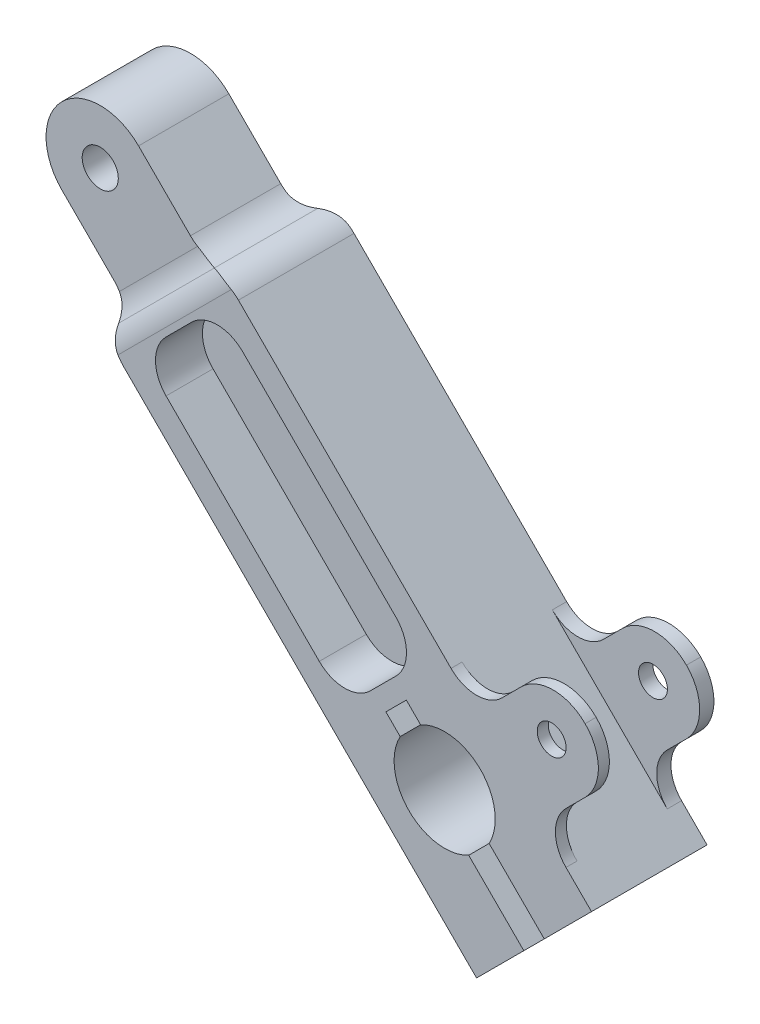
SolidWorks part; units mm, degrees
ref_plane "Front Plane" through (0, 0, 0) normal (0, 0, 1) x (1, 0, 0)
ref_plane "Top Plane" through (0, 0, 0) normal (0, 1, 0) x (1, 0, 0)
ref_plane "Right Plane" through (0, 0, 0) normal (1, 0, 0) x (0, 0, -1)
sketch "Sketch2" plane through (0, 0, 0) normal (0, 0, 1) x (1, 0, 0)
  line L0 (0, 0) -> (-234.0257, 0) construction
  line L1 (0, 0) -> (132.15, 132.15) construction
  line L2 (0, 0) -> (130.2279, -130.2279) construction
  line L3 (-10.6066, -10.6066) -> (10.6066, 10.6066) construction
  line L4 (-10.6066, -10.6066) -> (21.2132, -42.4264) construction
  line L5 (21.2132, -42.4264) -> (42.4264, -21.2132) construction
  line L6 (42.4264, -21.2132) -> (10.6066, 10.6066) construction
  line L7 (0, -21.2132) -> (21.2132, 0)
  line L9 (21.2132, 0) -> (53.033, -31.8198)
  line L10 (0, -21.2132) -> (31.8198, -53.033)
  line L11 (31.8198, -53.033) -> (26.5165, -58.3363)
  line L12 (114.318, -146.1378) -> (26.5165, -58.3363)
  line L13 (53.033, -31.8198) -> (58.3363, -26.5165)
  line L14 (128.4601, -96.6403) -> (58.3363, -26.5165)
  line L15 (146.1378, -114.318) -> (167.351, -93.1047)
  line L16 (167.351, -93.1047) -> (149.6733, -75.4271)
  line L17 (149.6733, -75.4271) -> (128.4601, -96.6403)
  line L18 (158.5121, -84.2659) -> (119.6213, -119.6213) construction
  line L19 (146.1378, -114.318) -> (160.2799, -128.4601)
  line L20 (114.318, -146.1378) -> (128.4601, -160.2799)
  line L21 (160.2799, -128.4601) -> (147.1984, -141.5416)
  line L22 (109.0147, -103.3578) -> (112.9628, -107.306)
  line L23 (103.3578, -109.0147) -> (109.0147, -103.3578)
  line L24 (103.3578, -109.0147) -> (107.306, -112.9628)
  line L25 (131.9365, -126.2797) -> (147.1984, -141.5416)
  line L26 (126.2797, -131.9365) -> (141.5416, -147.1984)
  line L27 (141.5416, -147.1984) -> (128.4601, -160.2799)
  line L28 (31.8198, -53.033) -> (53.033, -31.8198)
  line L29 (128.4601, -96.6403) -> (146.1378, -114.318)
  circle A0 centre (21.2132, -21.2132) radius 5
  circle A1 centre (149.2524, -92.6839) radius 4
  arc A2 (107.306, -112.9628) -> (126.2797, -131.9365) centre (119.6213, -119.6213) ccw
  arc A3 (131.9365, -126.2797) -> (112.9628, -107.306) centre (119.6213, -119.6213) ccw
  point P8 (0, 0)
  point P15 (10.6066, -10.6066)
  point P18 (130.2279, -130.2279)
  point P35 (111.5259, -126.9806)
  point P40 (106.1862, -106.1862)
  dimension "D4" = 10
  dimension "D5" = 15
  dimension "D12" = 8
  dimension "D13" = 12.5
  dimension "D14" = 28
  dimension "D1" = 184.17
  dimension "D2" = 30
  dimension "D3" = 45
  dimension "D6" = 15
  dimension "D7" = 30
  dimension "D8" = 45
  dimension "D9" = 45
  dimension "D10" = 30
  dimension "D11" = 25
  dimension "D15" = 20
  dimension "D17" = 19
extrude "Boss-Extrude1" add sketch "Sketch2" along normal blind 38 contours A3 L25 L21 L19 L29 L14 L13 L28 L11 L12 L20 L27 L26 A2 L24 L23 L22 region at (89.1363, -89.1363, 0)
extrude "Boss-Extrude2" add sketch "Sketch2<3>" along normal blind 6.5 contours L17 L29 L15 L16 A1 region at (139.4556, -86.4226, 0)
sketch "Sketch2<3>" plane through (0, 0, 0) normal (0, 0, 1) x (1, 0, 0) same geometry as "Sketch2"
fillet "Fillet1" radius 12.5 2 edges at (167.351, -93.1047, 3.25) (149.6733, -75.4271, 3.25)
ref_plane "Plane1" through (0, 0, 19) normal (0, 0, -1) x (-1, 0, 0)
mirror "Mirror1" about plane through (0, 0, 19) normal (0, 0, -1) of "Boss-Extrude2", "Fillet1"
sketch "Sketch3" plane through (42.4264, -42.4264, 0) normal (-0.7071, 0.7071, 0) x (0, 0, 1)
  line L0 (19, 73.5699) -> (19, -73.5699) construction
  line L1 (6.5, 15) -> (31.5, 15)
  line L2 (6.5, 15) -> (6.5, -15)
  line L3 (6.5, -15) -> (31.5, -15)
  line L4 (31.5, 15) -> (31.5, -15)
  line L5 (6.5, 15) -> (31.5, -15) construction
  line L6 (6.5, -15) -> (31.5, 15) construction
  point P0 (19, 0)
  dimension "D1" = 30
  dimension "D2" = 25
extrude "Boss-Extrude3" add sketch "Sketch3" along normal blind 45
sketch "Sketch4" plane through (0, 0, 31.5) normal (0, 0, 1) x (1, 0, 0)
  line L0 (10.6066, -10.6066) -> (31.8198, -31.8198) construction
  line L1 (0, -21.2132) -> (21.2132, 0) construction
  circle A0 centre (21.2132, -21.2132) radius 5
  dimension "D1" = 10
  dimension "D2" = 15
extrude "Cut-Extrude1" cut sketch "Sketch4" against normal through all
fillet "Fillet2" radius 15 2 edges at (21.2132, 0, 19) (0, -21.2132, 19)
sketch "Sketch5" plane through (144.37, -144.37, 0) normal (0.7071, -0.7071, 0) x (0, 0, -1)
  line L0 (-38, -13.25) -> (0, -13.25) construction
  line L1 (-38, -4) -> (-38, -22.5) construction
  line L2 (0, -4) -> (0, -22.5) construction
  circle A0 centre (-27, -13.25) radius 4
  circle A1 centre (-13, -13.25) radius 4
  dimension "D1" = 8
  dimension "D2" = 8
  dimension "D3" = 14
  dimension "D4" = 11
fillet "Fillet3" radius 10 4 edges at (128.4601, -96.6403, 34.75) (128.4601, -96.6403, 3.25) (146.1378, -114.318, 34.75) (146.1378, -114.318, 3.25)
sketch "Sketch8" plane through (-15.9099, -15.9099, 0) normal (-0.7071, -0.7071, 0) x (0, 0, 1)
  circle A0 centre (25.5207, -191.8383) radius 4.1672 construction
  circle A1 centre (25.5207, -151.8383) radius 4.1672 construction
  circle A2 centre (25.5207, -191.8383) radius 4.1672
  circle A3 centre (25.5207, -151.8383) radius 4.1672
extrude "Cut-Extrude4" cut sketch "Sketch8" against normal blind 10
sketch "Sketch9" plane through (0, 0, 0) normal (0, 0, -1) x (-1, 0, 0)
  line L0 (-128.4601, -160.2799) -> (-26.5165, -58.3363)
  line L1 (-128.4601, -160.2799) -> (-184.1342, -104.6058)
  line L2 (-26.5165, -58.3363) -> (-82.1906, -2.6622)
  line L3 (-184.1342, -104.6058) -> (-82.1906, -2.6622)
extrude "Cut-Extrude5" cut sketch "Sketch9" against normal up to surface (2.5515 mm away) contours L0 L1 L3 L2
sketch "Sketch10" plane through (0, 0, 38) normal (0, 0, 1) x (1, 0, 0)
  line L0 (128.4601, -160.2799) -> (26.5165, -58.3363)
  line L1 (128.4601, -160.2799) -> (184.01, -104.73)
  line L2 (26.5165, -58.3363) -> (82.0664, -2.7864)
  line L3 (184.01, -104.73) -> (82.0664, -2.7864)
extrude "Cut-Extrude6" cut sketch "Sketch10" against normal up to surface (3.4485 mm away)
sketch "Sketch11" plane through (0, 0, 2.5515) normal (0, 0, -1) x (-1, 0, 0)
  line L0 (-106.1862, -106.1862) -> (-42.4264, -42.4264)
  line L1 (-103.3578, -109.0147) -> (-109.0147, -103.3578) construction
  line L2 (-26.5165, -58.3363) -> (-58.3363, -26.5165) construction
  line L3 (-88.4485, -109.6617) -> (-109.6617, -88.4485)
  line L4 (-88.4485, -109.6617) -> (-38.951, -60.1642)
  line L5 (-109.6617, -88.4485) -> (-60.1642, -38.951)
  line L6 (-38.951, -60.1642) -> (-60.1642, -38.951)
  line L7 (-88.4485, -109.6617) -> (-60.1642, -38.951) construction
  line L8 (-109.6617, -88.4485) -> (-38.951, -60.1642) construction
  line L9 (-88.4485, -109.6617) -> (-109.6617, -88.4485)
  line L10 (-88.4485, -109.6617) -> (-91.984, -113.1972)
  line L11 (-109.6617, -88.4485) -> (-113.1972, -91.984)
  line L12 (-91.984, -113.1972) -> (-113.1972, -91.984)
  line L13 (-74.3063, -74.3063) -> (-63.6997, -84.9129)
  line L14 (-38.951, -60.1642) -> (-60.1642, -38.951)
  line L15 (-38.951, -60.1642) -> (-35.4154, -56.6286)
  line L16 (-60.1642, -38.951) -> (-56.6286, -35.4154)
  line L17 (-35.4154, -56.6286) -> (-56.6286, -35.4154)
  point P7 (-74.3063, -74.3063)
  dimension "D1" = 70
  dimension "D2" = 30
  dimension "D3" = 5
  dimension "D4" = 90
  dimension "D5" = 5
extrude "Cut-Extrude7" cut sketch "Sketch11" against normal blind 13 contours L4 L6 L0 L3 | L0 L6 L5 L3 | L12 L0 L3 L11 | L12 L10 L3 L0 | L13 L0 L3 L4 | L14 L15 L17 L16 region at (106.1261, -95.5195, 2.5515) region at (95.5195, -106.1261, 2.5515) region at (79.6096, -69.003, 2.5515) region at (81.3774, -91.984, 2.5515) region at (56.6286, -67.2352, 2.5515)
fillet "Fillet4" radius 10 4 edges at (91.984, -113.1972, 9.0515) (113.1972, -91.984, 9.0515) (35.4154, -56.6286, 9.0515) (56.6286, -35.4154, 9.0515)
fillet "Fillet6" radius 10 4 edges at (42.4264, -42.4264, 31.5) (31.8198, -53.033, 19) (53.033, -31.8198, 19) (42.4264, -42.4264, 6.5)
fillet "Fillet7" radius 10 4 edges at (42.4264, -42.4264, 34.5515) (58.3363, -26.5165, 18.5515) (26.5165, -58.3363, 18.5515) (42.4264, -42.4264, 2.5515)
ref_plane "Plane2" through (0, 0, 18.5515) normal (0, 0, -1) x (-1, 0, 0)
mirror "Mirror2" about plane through (0, 0, 18.5515) normal (0, 0, -1) of "Fillet4", "Cut-Extrude7"
